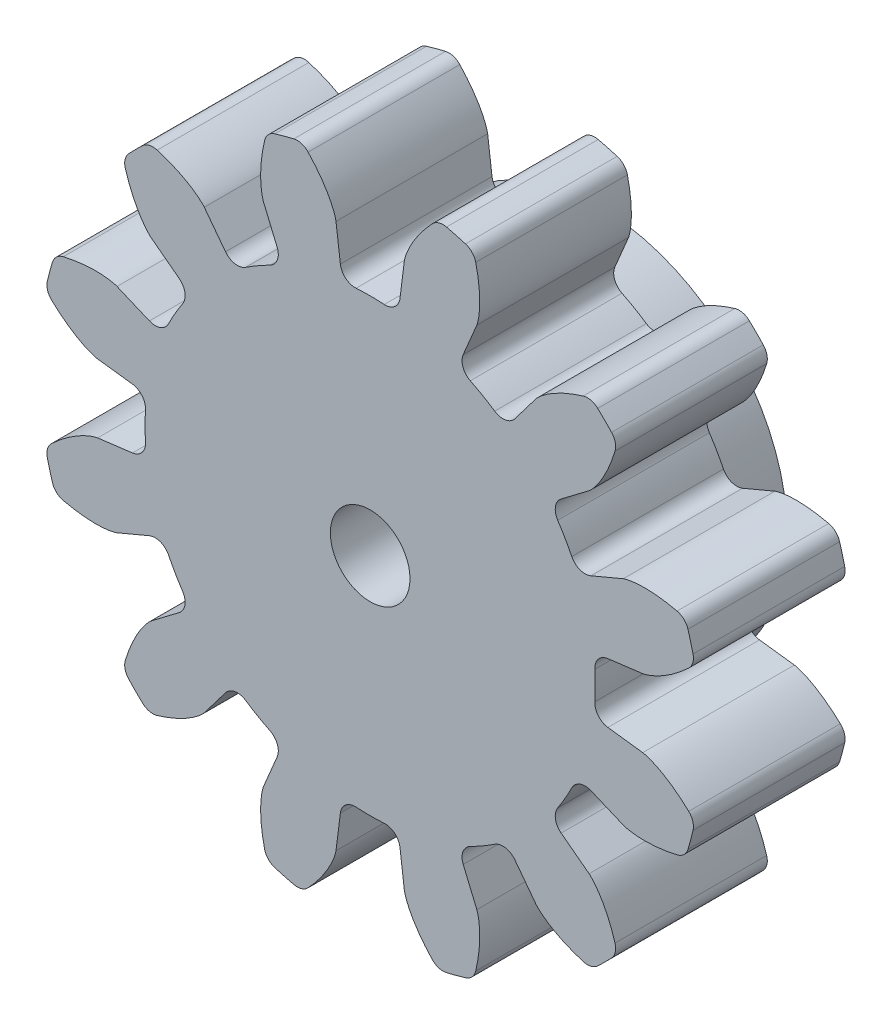
SolidWorks part; units mm, degrees
material "Brass"
ref_plane "Front Plane" through (0, 0, 0) normal (0, 0, 1) x (1, 0, 0)
ref_plane "Top Plane" through (0, 0, 0) normal (0, 1, 0) x (1, 0, 0)
ref_plane "Right Plane" through (0, 0, 0) normal (1, 0, 0) x (0, 0, -1)
sketch "Sketch1" plane through (0, 0, 0) normal (0, 0, 1) x (1, 0, 0)
  circle A0 centre (0, 0) radius 8.75
  dimension "D1" = 17.5
extrude "Boss-Extrude1" add sketch "Sketch1" along normal blind 4
sketch "Sketch2" plane through (0, 0, 4) normal (0, 0, 1) x (1, 0, 0)
  line L0 (7.1881, 0.9014) -> (0, 0) construction
  line L1 (0, 0) -> (7.1881, -0.9014) construction
  line L2 (5.8914, 0.7388) -> (7.1881, 0.9014)
  line L3 (5.8914, -0.7388) -> (7.1881, -0.9014)
  circle A0 centre (0, 0) radius 8.75 construction
  circle A1 centre (0, 0) radius 7.2444 construction
  circle A2 centre (0, 0) radius 7.5 construction
  circle A3 centre (0, 0) radius 5.9375 construction
  arc A4 (8.5637, 1.7962) -> (8.5637, -1.7962) centre (3.6281, 0) cw
  arc A5 (5.8914, -0.7388) -> (5.8914, 0.7388) centre (0, 0) ccw
  spline S0 degree 4 poles (7.1881, 0.9014) (7.1906, 0.9017) (7.1974, 0.9028) (7.2102, 0.9052) (7.231, 0.9098) (7.2574, 0.9165) (7.2912, 0.9262) (7.3308, 0.939) (7.374, 0.9543) (7.4206, 0.9724) (7.4667, 0.9918) (7.5124, 1.0122) (7.5575, 1.0337) (7.6118, 1.061) (7.6764, 1.0954) (7.7509, 1.1381) (7.8343, 1.1894) (7.9181, 1.2449) (7.9996, 1.302) (8.0806, 1.3625) (8.158, 1.4231) (8.2371, 1.489) (8.3094, 1.5512) (8.3888, 1.6241) (8.4524, 1.6838) (8.5346, 1.7659) (8.5825, 1.8154) (8.6381, 1.8744) (8.6624, 1.9012) (8.6774, 1.9177) knots 0 0 0 0 0 0.005377 0.015084 0.028532 0.04661 0.064855 0.092111 0.119476 0.146842 0.174209 0.201575 0.228941 0.256307 0.307035 0.361767 0.4165 0.471232 0.525964 0.580697 0.635429 0.690161 0.744894 0.799626 0.854358 0.909091 0.954545 1 1 1 1 1 construction
  spline S1 degree 4 poles (7.1881, 0.9014) (7.1906, 0.9017) (7.1974, 0.9028) (7.2102, 0.9052) (7.231, 0.9098) (7.2574, 0.9165) (7.2912, 0.9262) (7.3308, 0.939) (7.374, 0.9543) (7.4206, 0.9724) (7.4667, 0.9918) (7.5124, 1.0122) (7.5575, 1.0337) (7.6118, 1.061) (7.6764, 1.0954) (7.7509, 1.1381) (7.8343, 1.1894) (7.9181, 1.2449) (7.9996, 1.302) (8.0806, 1.3625) (8.158, 1.4231) (8.2371, 1.489) (8.3094, 1.5512) (8.3888, 1.6241) (8.4524, 1.6838) (8.5167, 1.7481) (8.5479, 1.7798) (8.5637, 1.7962) knots 0 0 0 0 0 0.005377 0.015084 0.028532 0.04661 0.064855 0.092111 0.119476 0.146842 0.174209 0.201575 0.228941 0.256307 0.307035 0.361767 0.4165 0.471232 0.525964 0.580697 0.635429 0.690161 0.744894 0.799626 0.854358 0.909091 0.909091 0.909091 0.909091 0.909091
  spline S2 degree 4 poles (7.1881, -0.9014) (7.1906, -0.9017) (7.1974, -0.9028) (7.2102, -0.9052) (7.231, -0.9098) (7.2574, -0.9165) (7.2912, -0.9262) (7.3308, -0.939) (7.374, -0.9543) (7.4206, -0.9724) (7.4667, -0.9918) (7.5124, -1.0122) (7.5575, -1.0337) (7.6118, -1.061) (7.6764, -1.0954) (7.7509, -1.1381) (7.8343, -1.1894) (7.9181, -1.2449) (7.9996, -1.302) (8.0806, -1.3625) (8.158, -1.4231) (8.2371, -1.489) (8.3094, -1.5512) (8.3888, -1.6241) (8.4524, -1.6838) (8.5346, -1.7659) (8.5825, -1.8154) (8.6381, -1.8744) (8.6624, -1.9012) (8.6774, -1.9177) knots 0 0 0 0 0 0.005377 0.015084 0.028532 0.04661 0.064855 0.092111 0.119476 0.146842 0.174209 0.201575 0.228941 0.256307 0.307035 0.361767 0.4165 0.471232 0.525964 0.580697 0.635429 0.690161 0.744894 0.799626 0.854358 0.909091 0.954545 1 1 1 1 1 construction
  spline S3 degree 4 poles (7.1881, -0.9014) (7.1906, -0.9017) (7.1974, -0.9028) (7.2102, -0.9052) (7.231, -0.9098) (7.2574, -0.9165) (7.2912, -0.9262) (7.3308, -0.939) (7.374, -0.9543) (7.4206, -0.9724) (7.4667, -0.9918) (7.5124, -1.0122) (7.5575, -1.0337) (7.6118, -1.061) (7.6764, -1.0954) (7.7509, -1.1381) (7.8343, -1.1894) (7.9181, -1.2449) (7.9996, -1.302) (8.0806, -1.3625) (8.158, -1.4231) (8.2371, -1.489) (8.3094, -1.5512) (8.3888, -1.6241) (8.4524, -1.6838) (8.5167, -1.7481) (8.5479, -1.7798) (8.5637, -1.7962) knots 0 0 0 0 0 0.005377 0.015084 0.028532 0.04661 0.064855 0.092111 0.119476 0.146842 0.174209 0.201575 0.228941 0.256307 0.307035 0.361767 0.4165 0.471232 0.525964 0.580697 0.635429 0.690161 0.744894 0.799626 0.854358 0.909091 0.909091 0.909091 0.909091 0.909091
  circle M4 centre (0, 0) radius 8.75
  dimension "D1" = 17.5
  dimension "D2" = 11.875
  dimension "D3" = 15
  dimension "D4" = 14.4889
extrude "Cut-Extrude1" cut sketch "Sketch2" against normal through all contours L3 S3 S1 L2 A5 M4 region at (7.5286, 0, 4)
sketch "Mate" plane through (0, 0, 0) normal (0, 0, 1) x (1, 0, 0)
  circle A0 centre (0, 0) radius 7.5
  circle A1 centre (0, 0) radius 7.5 construction
fillet "Fillet1" radius 0.3934 4 edges at (5.8914, -0.7388, 2) (5.8914, 0.7388, 2) (8.5637, -1.7962, 2) (8.5637, 1.7962, 2)
pattern_circular "CirPattern1" count 12 over 360 about axis through (0, 0, 0) along (0, 0, 1) of "Cut-Extrude1", "Fillet1"
sketch "Sketch4" plane through (0, 0, 0) normal (0, 0, 1) x (1, 0, 0)
  circle A0 centre (0, 0) radius 5
  dimension "D1" = 10
extrude "Boss-Extrude2" add sketch "Sketch4" against normal blind 2
sketch "Sketch3" plane through (0, 0, 0) normal (0, 0, 1) x (1, 0, 0)
  circle A0 centre (0, 0) radius 2.65
  dimension "D1" = 5.3
extrude "Cut-Extrude2" cut sketch "Sketch3" along normal blind 2 and the other way blind 2
sketch "Sketch5" plane through (0, 0, 0) normal (0, 0, 1) x (1, 0, 0)
  circle A0 centre (0, 0) radius 1.05
  dimension "D1" = 2.1
extrude "Cut-Extrude3" cut sketch "Sketch5" along normal through all
equation "\"DiametralPitch\"= 0.8"
equation "\"NumTeeth\"= 12"
equation "\"Addendum\"= 1 / \"DiametralPitch\""
equation "\"Dedendum\"= 1.25 / \"DiametralPitch\""
equation "\"WorkingDepth\"= 2 / \"DiametralPitch\""
equation "\"WholeDepth\"= 2.25 / \"DiametralPitch\""
equation "\"Clearance\"= 0.25 / \"DiametralPitch\""
equation "\"ToothThickness\"= 1.5708 / \"DiametralPitch\""
equation "\"CircularPitch\"= pi / \"DiametralPitch\""
equation "\"PitchCircle\"= \"NumTeeth\" / \"DiametralPitch\""
equation "\"OutsideDiameter\"= ( \"NumTeeth\" + 2 ) / \"DiametralPitch\""
equation "\"AddendumCircle\"= \"PitchCircle\" + ( 2 * \"Addendum\" )"
equation "\"DedendumCircle\"= \"PitchCircle\" - ( 2 * \"Dedendum\" )"
equation "\"PitchAngle\"= 360deg / \"NumTeeth\""
equation "\"PressureAngle\"= 15deg"
equation "\"Width\"= 4mm"
equation "\"Fillet\"= \"Clearance\" * cos ( \"PressureAngle\" ) * tan ( ( 90 + \"PressureAngle\" ) / 2 )"
equation "\"BaseCircle\"= \"PitchCircle\" * cos ( \"PressureAngle\" )"
equation "\"Alpha\"= sqr ( \"PitchCircle\" ^ 2 - \"BaseCircle\" ^ 2 ) / \"BaseCircle\" * 180 / PI - \"PressureAngle\""
equation "\"Beta\"= ( \"PitchAngle\" / 4 - \"Alpha\" )"
equation "\"Phi\"= sqr ( ( \"AddendumCircle\" / 2 ) ^ 2 - ( \"BaseCircle\" / 2 ) ^ 2 ) / ( \"BaseCircle\" / 2 )"
equation "\"D1@Sketch1\"=\"OutsideDiameter\""
equation "\"D1@Boss-Extrude1\"=\"Width\""
equation "\"D1@Sketch2\"=\"OutsideDiameter\""
equation "\"D2@Sketch2\"=\"DedendumCircle\""
equation "\"D3@Sketch2\"=\"PitchCircle\""
equation "\"D4@Sketch2\"=\"BaseCircle\""
equation "\"D1@Fillet1\"=\"Fillet\""
equation "\"D1@CirPattern1\"=\"NumTeeth\""
